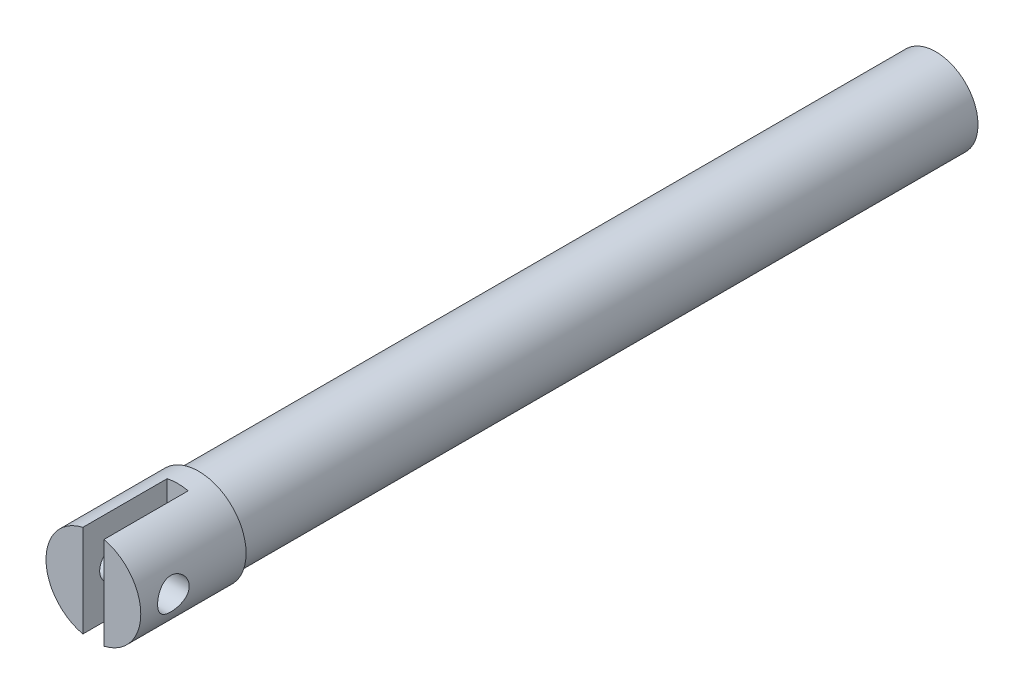
SolidWorks part; units mm, degrees
material "Cast Alloy Steel"
ref_plane "Front Plane" through (0, 0, 0) normal (0, 0, 1) x (1, 0, 0)
ref_plane "Top Plane" through (0, 0, 0) normal (0, 1, 0) x (1, 0, 0)
ref_plane "Right Plane" through (0, 0, 0) normal (1, 0, 0) x (0, 0, -1)
sketch "Sketch1" plane through (0, 0, 0) normal (0, 0, 1) x (1, 0, 0)
  circle A0 centre (0, 0) radius 4
  dimension "D1" = 8
extrude "Boss-Extrude1" add sketch "Sketch1" along normal blind 80 contours A0
sketch "Sketch2" plane through (0, 0, 80) normal (0, 0, 1) x (1, 0, 0)
  line L1 (1, -5.6777) -> (-1, -5.6777)
  line L2 (1, -5.6777) -> (1, 5.6777)
  line L3 (1, 5.6777) -> (-1, 5.6777)
  line L4 (-1, -5.6777) -> (-1, 5.6777)
  line L5 (1, -5.6777) -> (-1, 5.6777) construction
  line L6 (1, 5.6777) -> (-1, -5.6777) construction
  circle A0 centre (0, 0) radius 4.5
  circle M3 centre (0, 0) radius 4
  dimension "D2" = 9
  dimension "D1" = 2
extrude "Boss-Extrude2" add sketch "Sketch2" against normal blind 10 contours A0
extrude "Cut-Extrude2" cut sketch "Sketch2<3>" against normal blind 8 contours A0 L2 L3 L4 | L4 L2 M3 | A0 L4 L1 L2 | L4 A0 L2 M3 | L2 A0 L4 M3 region at (0, -5.0697, 80) region at (0, -4.21, 80) region at (0, 0, 80) region at (0, 4.21, 80) region at (0, 5.0697, 80)
sketch "Sketch2<3>" plane through (0, 0, 80) normal (0, 0, 1) x (1, 0, 0) same geometry as "Sketch2"
sketch "Sketch3" plane through (0, 0, 0) normal (1, 0, 0) x (0, 0, -1)
  circle A0 centre (-76.9014, 0) radius 1.5
  point P2 (-75.3237, 0)
  point P3 (-76.9014, 0)
  dimension "D1" = 3
extrude "Cut-Extrude3" cut sketch "Sketch3" against normal through all both and the other way through all contours A0
